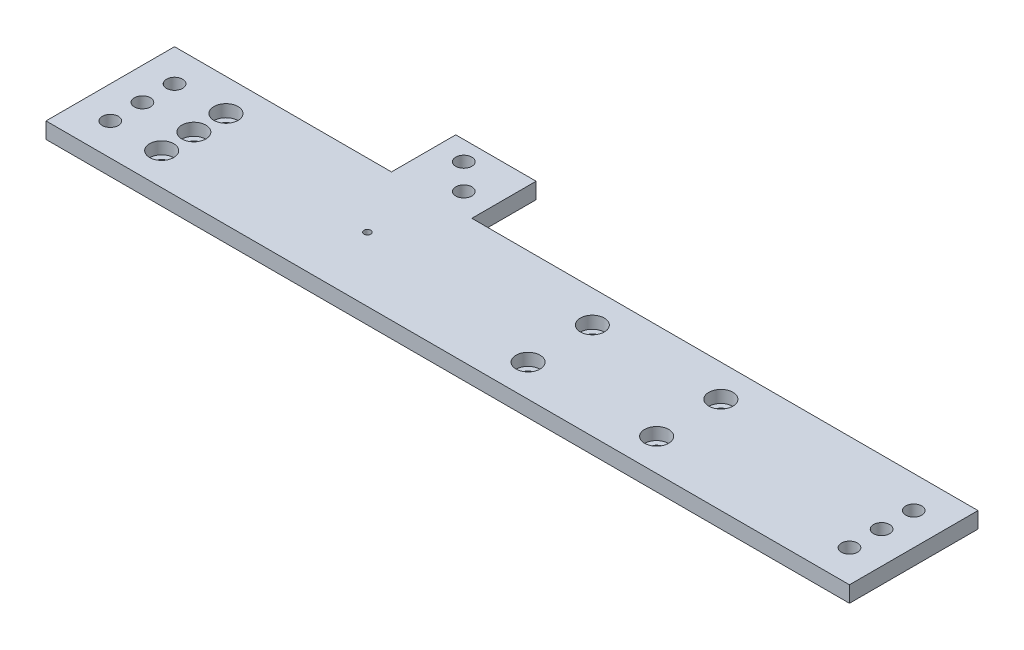
SolidWorks part; units mm, degrees
material "6061-T6 (SS)"
ref_plane "Front" through (0, 0, 0) normal (0, 0, 1) x (1, 0, 0)
ref_plane "Top" through (0, 0, 0) normal (0, 1, 0) x (1, 0, 0)
ref_plane "Right" through (0, 0, 0) normal (1, 0, 0) x (0, 0, -1)
sketch "Sketch1" plane through (0, 0, 0) normal (0, 1, 0) x (1, 0, 0)
  line L1 (-158.75, -25.4) -> (158.75, -25.4)
  line L2 (-158.75, -25.4) -> (-158.75, 25.4)
  line L3 (-158.75, 25.4) -> (158.75, 25.4)
  line L4 (158.75, -25.4) -> (158.75, 25.4)
  line L5 (-158.75, -25.4) -> (158.75, 25.4) construction
  line L6 (-158.75, 25.4) -> (158.75, -25.4) construction
  point P0 (0, 0)
  dimension "D1" = 50.8
  dimension "D2" = 317.5
extrude "Boss-Extrude1" add sketch "Sketch1" along normal blind 6.35
hole_wizard "CBORE for #10 Socket Head Cap Screw1" positions "Sketch2" profile "Sketch4" counterbore size "#10" standard "ANSI Inch" end condition through all
sketch "Sketch2" plane through (0, 6.35, 0) normal (0, 1, 0) x (1, 0, 0)
  line L2 (158.75, 25.4) -> (-158.75, 25.4) construction
  line L6 (-158.75, -25.4) -> (158.75, -25.4) construction
  line L8 (-158.75, 25.4) -> (-158.75, -25.4) construction
  line L12 (158.75, -25.4) -> (158.75, 25.4) construction
  line L15 (19.05, 12.7) -> (19.05, 25.4) construction
  line L17 (19.05, -12.7) -> (19.05, -25.4) construction
  line L18 (-125.73, -25.4) -> (-125.73, -12.7) construction
  line L20 (-125.73, 0) -> (-125.73, 12.7) construction
  line L21 (-125.73, 12.7) -> (-125.73, 25.4) construction
  line L22 (-125.73, 0) -> (-125.73, -12.7) construction
  point P64 (19.05, 12.7)
  point P66 (69.85, 12.7)
  point P68 (19.05, -12.7)
  point P70 (69.85, -12.7)
  point P92 (-125.73, 12.7)
  point P94 (-125.73, 0)
  point P102 (-125.73, -12.7)
  dimension "D2" = 50.8
  dimension "D3" = 25.4
  dimension "D4" = 88.9
  dimension "D5" = 33.02
sketch "Sketch4" plane through (-125.73, 6.35, 12.7) normal (1, 0, 0) x (0, 0, 1)
  line L0 (0, 0) -> (0, 6.35)
  line L1 (0, 6.35) -> (2.5527, 6.35)
  line L3 (2.5527, 6.35) -> (2.5527, 4.826)
  line L4 (2.5527, 4.826) -> (4.7625, 4.826)
  line L5 (4.7625, 4.826) -> (4.7625, 0)
  line L7 (4.7625, 0) -> (0, 0)
  line L11 (0, -6.35) -> (0, 107.95) construction
  dimension "Thru Hole Dia." = 5.1054
  dimension "Thru Hole Depth" = 6.35
  dimension "C'Bore Dia." = 9.525
  dimension "C'Bore Depth" = 4.826
sketch "Sketch7" plane through (0, 0, 0) normal (0, -1, 0) x (1, 0, 0)
  line L0 (-146.05, 25.4) -> (-146.05, 12.7) construction
  line L1 (-158.75, 25.4) -> (158.75, 25.4) construction
  line L2 (-146.05, 12.7) -> (-146.05, 0) construction
  line L3 (-146.05, 0) -> (-146.05, -12.7) construction
  line L4 (-146.05, -12.7) -> (-146.05, -25.4) construction
  line L5 (158.75, -25.4) -> (-158.75, -25.4) construction
  line L7 (-158.75, -25.4) -> (-158.75, 25.4) construction
  line L8 (146.05, 25.4) -> (146.05, 12.7) construction
  line L9 (146.05, 12.7) -> (146.05, 0) construction
  line L10 (146.05, 0) -> (146.05, -12.7) construction
  line L11 (146.05, -12.7) -> (146.05, -25.4) construction
  line L13 (158.75, 25.4) -> (158.75, -25.4) construction
  point P0 (-146.05, 12.7)
  point P2 (-146.05, 0)
  point P4 (-146.05, -12.7)
  point P6 (146.05, 12.7)
  point P8 (146.05, 0)
  point P10 (146.05, -12.7)
  dimension "D1" = 12.7
  dimension "D2" = 12.7
hole_wizard "1/4 (0.25) Diameter Hole1" positions "Sketch7" profile "Sketch6" hole size "1/4" standard "ANSI Inch" end condition through all
sketch "Sketch6" plane through (-146.05, 0, 12.7) normal (1, 0, 0) x (0, 0, -1)
  line L0 (0, 0) -> (0, 6.35)
  line L1 (0, 6.35) -> (3.175, 6.35)
  line L2 (3.175, 6.35) -> (3.175, 0)
  line L5 (3.175, 0) -> (0, 0)
  line L11 (0, -6.35) -> (0, 107.95) construction
  dimension "Thru Hole Dia." = 6.35
  dimension "Thru Hole Depth" = 6.35
sketch "Sketch10" plane through (0, 0, 0) normal (0, -1, 0) x (-1, 0, 0)
  line L0 (158.75, 25.4) -> (158.75, -25.4) construction
  point P0 (57.15, 0)
  dimension "D1" = 101.6
hole_wizard "#6-32 Tapped Hole1" positions "Sketch10" profile "Sketch9" tap size "#6-32" standard "ANSI Inch" end condition through all
sketch "Sketch9" plane through (-57.15, 0, 0) normal (1, 0, 0) x (0, 0, -1)
  line L0 (0, 0) -> (0, 6.35)
  line L1 (0, 6.35) -> (1.3525, 6.35)
  line L2 (1.3525, 6.35) -> (1.3525, 0)
  line L5 (1.3525, 0) -> (0, 0)
  line L11 (0, -6.35) -> (0, 107.95) construction
  dimension "Thru Tap Drill Dia." = 2.7051
  dimension "Thru Tap Drill Depth" = 6.35
cosmetic thread "Hole Thread1" parameters "D2"=3.5052
sketch "Sketch11" plane through (0, 0, 0) normal (0, -1, 0) x (1, 0, 0)
  line L0 (158.75, -25.4) -> (-158.75, -25.4) construction
  line L1 (-70.0118, -25.4) -> (-48.1024, -25.4)
  line L2 (-70.0118, -25.4) -> (-70.0118, -45.81)
  line L3 (-70.0118, -45.81) -> (-48.1024, -45.81)
  line L4 (-48.1024, -25.4) -> (-48.1024, -45.81)
extrude "Boss-Extrude2" [suppressed] add sketch "Sketch11" against normal up to surface (6.35 mm away) up to face at (-57.15, 6.35, -1.3526)
sketch "Sketch12" plane through (0, 6.35, 0) normal (0, 1, 0) x (1, 0, 0)
  line L5 (-158.75, 25.4) -> (-158.75, -25.4) construction
  line L6 (-73.025, 25.4) -> (-73.025, 50.8)
  line L7 (158.75, 25.4) -> (-158.75, 25.4) construction
  line L8 (-73.025, 50.8) -> (-41.275, 50.8)
  line L9 (-41.275, 50.8) -> (-41.275, 25.4)
  line L10 (-73.025, 25.4) -> (-41.275, 25.4)
  dimension "D4" = 85.725
  dimension "D5" = 25.4
  dimension "D6" = 31.75
extrude "Boss-Extrude3" add sketch "Sketch12" against normal up to surface (6.35 mm away) up to face at (-57.15, 0, -1.3526)
sketch "Sketch15" plane through (0, 0, 0) normal (0, -1, 0) x (-1, 0, 0)
  point P0 (62.23, 43.18)
  point P3 (52.07, 33.02)
hole_wizard "1/4 (0.25) Diameter Hole2" positions "Sketch15" profile "Sketch14" hole size "1/4" standard "ANSI Inch" end condition through all
sketch "Sketch14" plane through (-62.23, 0, -43.18) normal (1, 0, 0) x (0, 0, -1)
  line L0 (0, 0) -> (0, 6.35)
  line L1 (0, 6.35) -> (3.175, 6.35)
  line L2 (3.175, 6.35) -> (3.175, 0)
  line L5 (3.175, 0) -> (0, 0)
  line L11 (0, -6.35) -> (0, 107.95) construction
  dimension "Thru Hole Dia." = 6.35
  dimension "Thru Hole Depth" = 6.35
